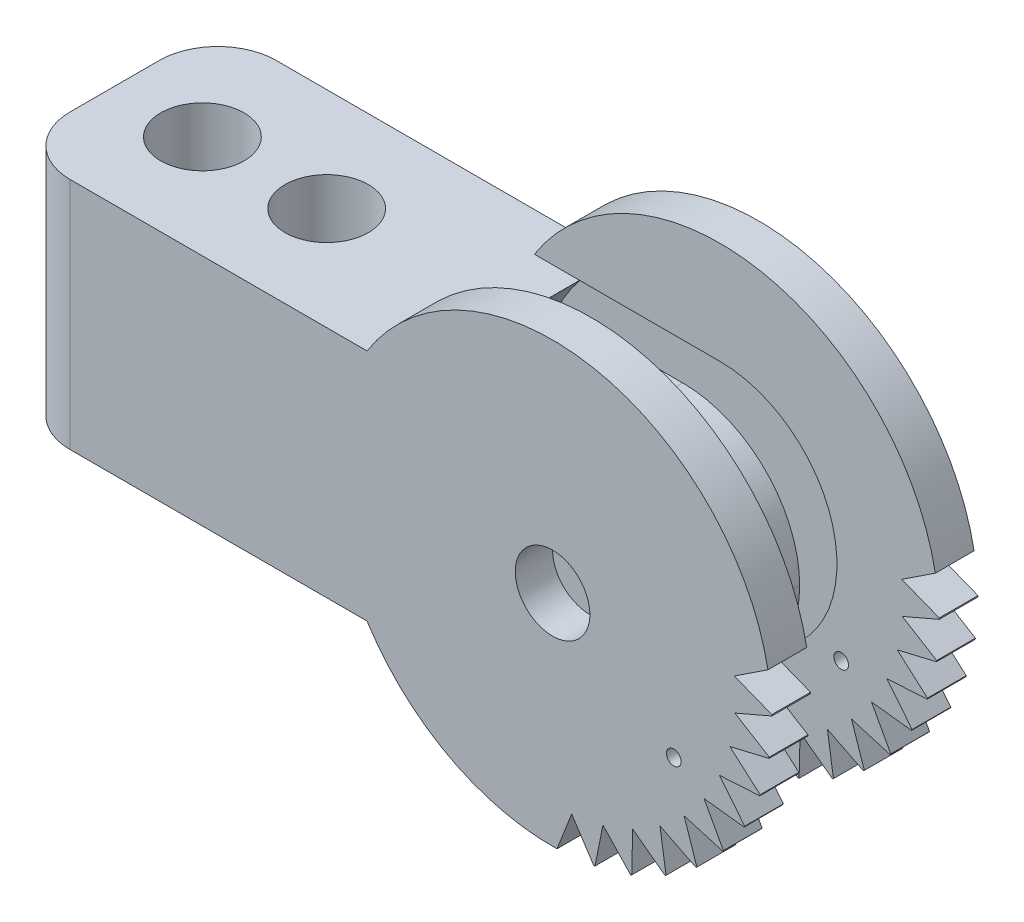
SolidWorks part; units mm, degrees
ref_plane "Front Plane" through (0, 0, 0) normal (0, 0, 1) x (1, 0, 0)
ref_plane "Top Plane" through (0, 0, 0) normal (0, 1, 0) x (1, 0, 0)
ref_plane "Right Plane" through (0, 0, 0) normal (1, 0, 0) x (0, 0, -1)
sketch "Sketch1" plane through (0, 0, 0) normal (0, 0, 1) x (1, 0, 0)
  line L1 (-37, 8) -> (8, 8)
  line L2 (-37, 8) -> (-37, -8)
  line L3 (-37, -8) -> (8, -8)
  line L4 (8, 8) -> (8, -8)
  dimension "D1" = 16
  dimension "D2" = 45
  dimension "D3" = 8
  dimension "D4" = 8
extrude "Boss-Extrude1" add sketch "Sketch1" along normal blind 14.1 contours L1 L4 L3 L2
fillet "Fillet1" radius 8 2 edges at (8, -8, 7.05) (8, 8, 7.05)
sketch "Sketch2" plane through (0, -8, 0) normal (0, -1, 0) x (1, 0, 0)
  line L0 (-37, 14.1) -> (-37, 0) construction
  line L1 (-37, 14.1) -> (0, 14.1) construction
  circle A0 centre (-31, 7.05) radius 1.65
  circle A1 centre (-22.5, 7.05) radius 1.65
  dimension "D1" = 3.3
  dimension "D2" = 6
  dimension "D4" = 3.3
  dimension "D3" = 7.05
  dimension "D5" = 8.5
extrude "Cut-Extrude1" cut sketch "Sketch2" against normal blind 21.1 contours A1 | A0 region at (-22.5, -8, 7.05)
ref_plane "Plane1" through (0, 0, 2.55) normal (0, 0, -1) x (-1, 0, 0)
sketch "Sketch4" plane through (0, 0, 2.55) normal (0, 0, -1) x (-1, 0, 0)
  circle A0 centre (0, 0) radius 12.5
  dimension "D1" = 25
extrude "Cut-Extrude2" cut sketch "Sketch4" against normal blind 2.65 contours A0
ref_plane "Plane2" through (0, 0, 7.05) normal (0, 0, -1) x (-1, 0, 0)
mirror "Mirror1" about plane through (0, 0, 7.05) normal (0, 0, -1) of "Cut-Extrude2"
sketch "Sketch6" plane through (0, 0, 0) normal (0, 0, -1) x (-1, 0, 0)
  circle A0 centre (0, 0) radius 15
  arc M1 (0, 8) -> (-8, 0) centre (0, 0) ccw
  arc M2 (-8, 0) -> (0, -8) centre (0, 0) ccw
  line M3 (0, -8) -> (37, -8)
  line M5 (37, 8) -> (0, 8)
  dimension "D1" = 30
extrude "Boss-Extrude3" add sketch "Sketch6" against normal blind 2.65 contours A0 M5 M3 M2 M1 region at (-6.3443, 8.4082, 0)
sketch "Sketch7" plane through (0, 0, 0) normal (0, 0, -1) x (-1, 0, 0)
  line L0 (0, 0) -> (-15, 0) construction
  line L1 (0, 0) -> (-12.5185, -8.4438) construction
  line L2 (0, 0) -> (-13.2068, -7.3206) construction
  line L3 (0, 0) -> (-13.7945, -6.1417) construction
  line L4 (0, 0) -> (-14.2773, -4.9161) construction
  line L5 (0, 0) -> (-14.6515, -3.653) construction
  line L6 (0, 0) -> (-14.9141, -2.3622) construction
  line L7 (0, 0) -> (-15.0632, -1.0533) construction
  line L8 (0, 0) -> (-15.0977, 0.2635) construction
  line L9 (0, 0) -> (-15.0173, 1.5784) construction
  line L10 (0, 0) -> (-14.8226, 2.8812) construction
  line L11 (0, 0) -> (-14.5151, 4.1621) construction
  line L12 (0, 0) -> (-14.0971, 5.4114) construction
  line L13 (0, 0) -> (-13.5718, 6.6194) construction
  line L14 (0, 0) -> (-12.9432, 7.7771) construction
  line L15 (0, 0) -> (-12.2162, 8.8756) construction
  line L16 (0, 0) -> (-11.3961, 9.9065) construction
  line L17 (0, 0) -> (-10.4893, 10.862) construction
  line L18 (0, 0) -> (-9.5027, 11.7349) construction
  line L19 (0, 0) -> (-8.4438, 12.5185) construction
  line L20 (0, 0) -> (-7.3206, 13.2068) construction
  line L21 (0, 0) -> (-6.1417, 13.7945) construction
  line L22 (0, 0) -> (-4.9161, 14.2773) construction
  line L23 (0, 0) -> (-3.653, 14.6515) construction
  line L24 (0, 0) -> (-2.3622, 14.9141) construction
  line L25 (0, 0) -> (-1.0533, 15.0632) construction
  line L26 (0, 0) -> (0.2635, 15.0977) construction
  line L27 (0, 0) -> (1.5784, 15.0173) construction
  line L28 (0, 0) -> (2.8812, 14.8226) construction
  line L29 (0, 0) -> (4.1621, 14.5151) construction
  line L30 (0, 0) -> (5.4114, 14.0971) construction
  line L31 (0, 0) -> (6.6194, 13.5718) construction
  line L32 (0, 0) -> (7.7771, 12.9432) construction
  line L33 (0, 0) -> (8.8756, 12.2162) construction
  line L34 (0, 0) -> (9.9065, 11.3961) construction
  line L35 (0, 0) -> (10.862, 10.4893) construction
  line L36 (0, 0) -> (11.7349, 9.5027) construction
  line L37 (0, 0) -> (12.5185, 8.4438) construction
  line L38 (0, 0) -> (13.2068, 7.3206) construction
  line L39 (0, 0) -> (13.7945, 6.1417) construction
  line L40 (0, 0) -> (14.2773, 4.9161) construction
  line L41 (0, 0) -> (14.6515, 3.653) construction
  line L42 (0, 0) -> (14.9141, 2.3622) construction
  line L43 (0, 0) -> (15.0632, 1.0533) construction
  line L44 (0, 0) -> (15.0977, -0.2635) construction
  line L45 (0, 0) -> (15.0173, -1.5784) construction
  line L46 (0, 0) -> (14.8226, -2.8812) construction
  line L47 (0, 0) -> (14.5151, -4.1621) construction
  line L48 (0, 0) -> (14.0971, -5.4114) construction
  line L49 (0, 0) -> (13.5718, -6.6194) construction
  line L50 (0, 0) -> (12.9432, -7.7771) construction
  line L51 (0, 0) -> (12.2162, -8.8756) construction
  line L52 (0, 0) -> (11.3961, -9.9065) construction
  line L53 (0, 0) -> (10.4893, -10.862) construction
  line L54 (0, 0) -> (9.5027, -11.7349) construction
  line L55 (0, 0) -> (8.4438, -12.5185) construction
  line L56 (0, 0) -> (7.3206, -13.2068) construction
  line L57 (0, 0) -> (6.1417, -13.7945) construction
  line L58 (0, 0) -> (4.9161, -14.2773) construction
  line L59 (0, 0) -> (3.653, -14.6515) construction
  line L60 (0, 0) -> (2.3622, -14.9141) construction
  line L61 (0, 0) -> (1.0533, -15.0632) construction
  line L62 (0, 0) -> (-0.2635, -15.0977) construction
  line L63 (0, 0) -> (-1.5784, -15.0173) construction
  line L64 (0, 0) -> (-2.8812, -14.8226) construction
  line L65 (0, 0) -> (-4.1621, -14.5151) construction
  line L66 (0, 0) -> (-5.4114, -14.0971) construction
  line L67 (0, 0) -> (-6.6194, -13.5718) construction
  line L68 (0, 0) -> (-7.7771, -12.9432) construction
  line L69 (0, 0) -> (-8.8756, -12.2162) construction
  line L70 (0, 0) -> (-9.9065, -11.3961) construction
  line L71 (0, 0) -> (-10.862, -10.4893) construction
  line L72 (0, 0) -> (-11.7349, -9.5027) construction
  line L73 (-13.2068, -7.3206) -> (-10.363, -6.9899)
  line L74 (-10.363, -6.9899) -> (-11.7349, -9.5027)
  line L75 (-13.2068, -7.3206) -> (-11.7349, -9.5027)
  line L76 (-11.4193, -5.0842) -> (-13.2068, -7.3206)
  line L77 (-14.2773, -4.9161) -> (-11.4193, -5.0842)
  line L78 (-14.2773, -4.9161) -> (-13.2068, -7.3206)
  line L79 (-12.1287, -3.024) -> (-14.2773, -4.9161)
  line L80 (-14.9141, -2.3622) -> (-12.1287, -3.024)
  line L81 (-14.9141, -2.3622) -> (-14.2773, -4.9161)
  line L82 (-12.4696, -0.872) -> (-14.9141, -2.3622)
  line L83 (-15.0977, 0.2635) -> (-12.4696, -0.872)
  line L84 (-15.0977, 0.2635) -> (-14.9141, -2.3622)
  line L85 (-12.4315, 1.3066) -> (-15.0977, 0.2635)
  line L86 (-14.8226, 2.8812) -> (-12.4315, 1.3066)
  line L87 (-14.8226, 2.8812) -> (-15.0977, 0.2635)
  line L88 (-12.0158, 3.4455) -> (-14.8226, 2.8812)
  line L89 (-14.0971, 5.4114) -> (-12.0158, 3.4455)
  line L90 (-14.0971, 5.4114) -> (-14.8226, 2.8812)
  line L91 (-11.2349, 5.4796) -> (-14.0971, 5.4114)
  line L92 (-12.9432, 7.7771) -> (-11.2349, 5.4796)
  line L93 (-12.9432, 7.7771) -> (-14.0971, 5.4114)
  line L94 (-10.1127, 7.3473) -> (-12.9432, 7.7771)
  line L95 (-11.3961, 9.9065) -> (-10.1127, 7.3473)
  line L96 (-11.3961, 9.9065) -> (-12.9432, 7.7771)
  line L97 (-8.6832, 8.9917) -> (-11.3961, 9.9065)
  line L98 (-9.5027, 11.7349) -> (-8.6832, 8.9917)
  line L99 (-9.5027, 11.7349) -> (-11.3961, 9.9065)
  line L100 (-6.9899, 10.363) -> (-9.5027, 11.7349)
  line L101 (-7.3206, 13.2068) -> (-6.9899, 10.363)
  line L102 (-7.3206, 13.2068) -> (-9.5027, 11.7349)
  line L103 (-5.0842, 11.4193) -> (-7.3206, 13.2068)
  line L104 (-4.9161, 14.2773) -> (-5.0842, 11.4193)
  line L105 (-4.9161, 14.2773) -> (-7.3206, 13.2068)
  line L106 (-3.024, 12.1287) -> (-4.9161, 14.2773)
  line L107 (-2.3622, 14.9141) -> (-3.024, 12.1287)
  line L108 (-2.3622, 14.9141) -> (-4.9161, 14.2773)
  line L109 (-0.872, 12.4696) -> (-2.3622, 14.9141)
  line L110 (0.2635, 15.0977) -> (-0.872, 12.4696)
  line L111 (0.2635, 15.0977) -> (-2.3622, 14.9141)
  line L112 (1.3066, 12.4315) -> (0.2635, 15.0977)
  line L113 (2.8812, 14.8226) -> (1.3066, 12.4315)
  line L114 (2.8812, 14.8226) -> (0.2635, 15.0977)
  line L115 (3.4455, 12.0158) -> (2.8812, 14.8226)
  line L116 (5.4114, 14.0971) -> (3.4455, 12.0158)
  line L117 (5.4114, 14.0971) -> (2.8812, 14.8226)
  line L118 (5.4796, 11.2349) -> (5.4114, 14.0971)
  line L119 (7.7771, 12.9432) -> (5.4796, 11.2349)
  line L120 (7.7771, 12.9432) -> (5.4114, 14.0971)
  line L121 (7.3473, 10.1127) -> (7.7771, 12.9432)
  line L122 (9.9065, 11.3961) -> (7.3473, 10.1127)
  line L123 (9.9065, 11.3961) -> (7.7771, 12.9432)
  line L124 (8.9917, 8.6832) -> (9.9065, 11.3961)
  line L125 (11.7349, 9.5027) -> (8.9917, 8.6832)
  line L126 (11.7349, 9.5027) -> (9.9065, 11.3961)
  line L127 (10.363, 6.9899) -> (11.7349, 9.5027)
  line L128 (13.2068, 7.3206) -> (10.363, 6.9899)
  line L129 (13.2068, 7.3206) -> (11.7349, 9.5027)
  line L130 (11.4193, 5.0842) -> (13.2068, 7.3206)
  line L131 (14.2773, 4.9161) -> (11.4193, 5.0842)
  line L132 (14.2773, 4.9161) -> (13.2068, 7.3206)
  line L133 (12.1287, 3.024) -> (14.2773, 4.9161)
  line L134 (14.9141, 2.3622) -> (12.1287, 3.024)
  line L135 (14.9141, 2.3622) -> (14.2773, 4.9161)
  line L136 (12.4696, 0.872) -> (14.9141, 2.3622)
  line L137 (15.0977, -0.2635) -> (12.4696, 0.872)
  line L138 (15.0977, -0.2635) -> (14.9141, 2.3622)
  line L139 (12.4315, -1.3066) -> (15.0977, -0.2635)
  line L140 (14.8226, -2.8812) -> (12.4315, -1.3066)
  line L141 (14.8226, -2.8812) -> (15.0977, -0.2635)
  line L142 (12.0158, -3.4455) -> (14.8226, -2.8812)
  line L143 (14.0971, -5.4114) -> (12.0158, -3.4455)
  line L144 (14.0971, -5.4114) -> (14.8226, -2.8812)
  line L145 (11.2349, -5.4796) -> (14.0971, -5.4114)
  line L146 (12.9432, -7.7771) -> (11.2349, -5.4796)
  line L147 (12.9432, -7.7771) -> (14.0971, -5.4114)
  line L148 (10.1127, -7.3473) -> (12.9432, -7.7771)
  line L149 (11.3961, -9.9065) -> (10.1127, -7.3473)
  line L150 (11.3961, -9.9065) -> (12.9432, -7.7771)
  line L151 (8.6832, -8.9917) -> (11.3961, -9.9065)
  line L152 (9.5027, -11.7349) -> (8.6832, -8.9917)
  line L153 (9.5027, -11.7349) -> (11.3961, -9.9065)
  line L154 (6.9899, -10.363) -> (9.5027, -11.7349)
  line L155 (7.3206, -13.2068) -> (6.9899, -10.363)
  line L156 (7.3206, -13.2068) -> (9.5027, -11.7349)
  line L157 (5.0842, -11.4193) -> (7.3206, -13.2068)
  line L158 (4.9161, -14.2773) -> (5.0842, -11.4193)
  line L159 (4.9161, -14.2773) -> (7.3206, -13.2068)
  line L160 (3.024, -12.1287) -> (4.9161, -14.2773)
  line L161 (2.3622, -14.9141) -> (3.024, -12.1287)
  line L162 (2.3622, -14.9141) -> (4.9161, -14.2773)
  line L163 (0.872, -12.4696) -> (2.3622, -14.9141)
  line L164 (-0.2635, -15.0977) -> (0.872, -12.4696)
  line L165 (-0.2635, -15.0977) -> (2.3622, -14.9141)
  line L166 (-1.3066, -12.4315) -> (-0.2635, -15.0977)
  line L167 (-2.8812, -14.8226) -> (-1.3066, -12.4315)
  line L168 (-2.8812, -14.8226) -> (-0.2635, -15.0977)
  line L169 (-3.4455, -12.0158) -> (-2.8812, -14.8226)
  line L170 (-5.4114, -14.0971) -> (-3.4455, -12.0158)
  line L171 (-5.4114, -14.0971) -> (-2.8812, -14.8226)
  line L172 (-5.4796, -11.2349) -> (-5.4114, -14.0971)
  line L173 (-7.7771, -12.9432) -> (-5.4796, -11.2349)
  line L174 (-7.7771, -12.9432) -> (-5.4114, -14.0971)
  line L175 (-7.3473, -10.1127) -> (-7.7771, -12.9432)
  line L176 (-9.9065, -11.3961) -> (-7.3473, -10.1127)
  line L177 (-9.9065, -11.3961) -> (-7.7771, -12.9432)
  line L178 (-8.9917, -8.6832) -> (-9.9065, -11.3961)
  line L179 (-11.7349, -9.5027) -> (-8.9917, -8.6832)
  line L180 (-11.7349, -9.5027) -> (-9.9065, -11.3961)
  arc A0 (12.6886, 8) -> (12.6886, -8) centre (0, 0) ccw construction
  circle A1 centre (-8.2904, -5.5919) radius 0.5
  point P6 (-10.363, -6.9899)
  point P81 (0, 0)
  point P189 (0, 0)
  arc M75 (12.6886, 8) -> (12.6886, -8) centre (0, 0) ccw
  dimension "D6" = 1
  dimension "D1" = 34
  dimension "D3" = 12.5
  dimension "D4" = 15.1
  dimension "D7" = 10
  dimension "D2" = 72
  dimension "D5" = 36
extrude "Cut-Extrude3" cut sketch "Sketch7" against normal blind 2.65 contours L74 L73 M75 | L179 L178 M75 | L176 L175 M75 | L173 L172 M75 | L170 L169 M75 | L80 L79 M75 | L83 L82 M75 | A1 | L167 L166 M75 | L86 L85 M75 | L76 L78 L77 region at (11.7348, -7.9152, 0) region at (10.182, -9.8327, 0) region at (13.7343, -3.4243, 0) region at (8.3199, -11.4514, 0) region at (14.1202, -0.9874, 0) region at (6.205, -12.7222, 0) region at (14.0772, 1.4796, 0) region at (3.9016, -13.6064, 0) region at (1.4796, -14.0772, 0) region at (8.2904, -5.5919, 0)
mirror "Mirror8" about plane through (0, 0, 7.05) normal (0, 0, -1) of "Cut-Extrude3", "Boss-Extrude3"
fillet "Fillet2" radius 4 2 edges at (-37, 0, 14.1) (-37, 0, 0)
sketch "Sketch8" plane through (0, 0, 0) normal (0, 0, -1) x (-1, 0, 0)
  circle A0 centre (0, 0) radius 2.55
  dimension "D1" = 5.1
extrude "Cut-Extrude4" cut sketch "Sketch8" against normal blind 21.65 contours A0
sketch "Sketch9" plane through (0, 8, 0) normal (0, 1, 0) x (1, 0, 0)
  circle A0 centre (-31, -7.05) radius 2.85
  circle A1 centre (-22.5, -7.05) radius 2.85
  dimension "D1" = 5.7
  dimension "D2" = 5.7
extrude "Cut-Extrude5" cut sketch "Sketch9" against normal blind 6
